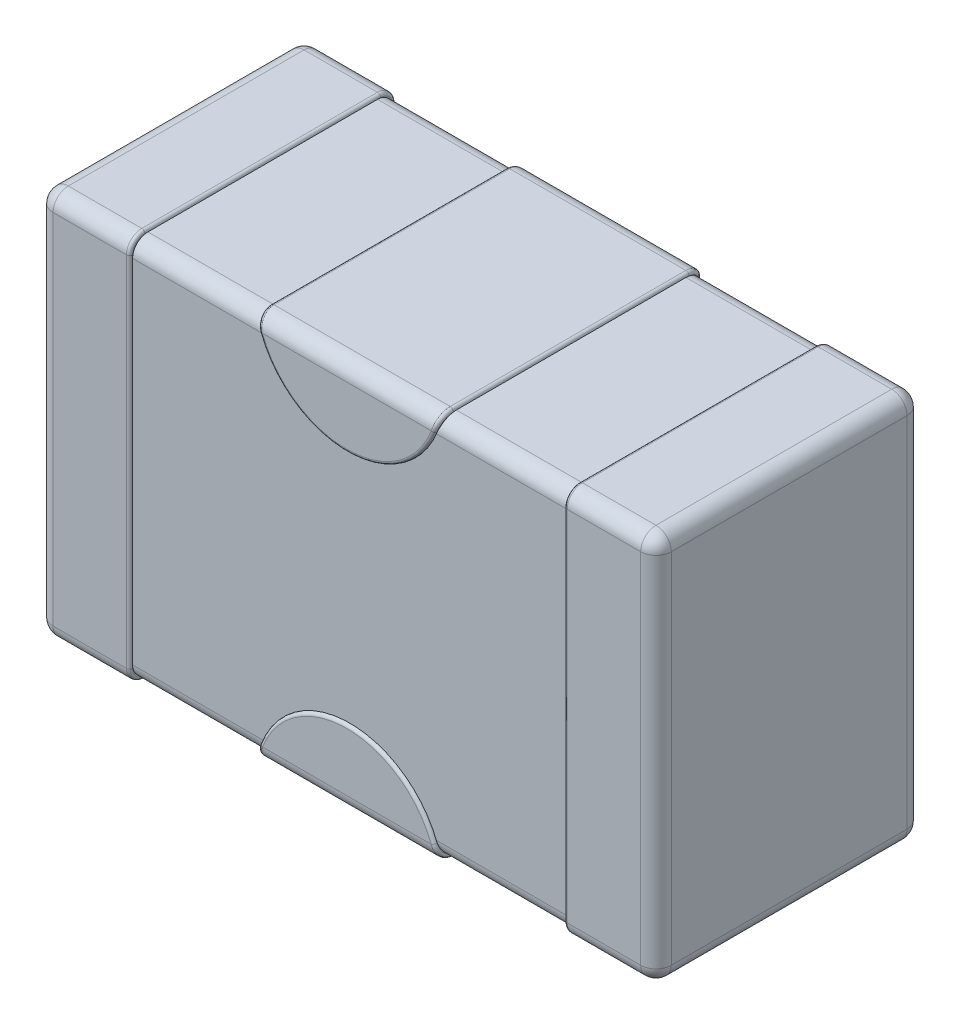
SolidWorks part; units mm, degrees
ref_plane "Front Plane" through (0, 0, 0) normal (0, 0, 1) x (1, 0, 0)
ref_plane "Top Plane" through (0, 0, 0) normal (0, 1, 0) x (1, 0, 0)
ref_plane "Right Plane" through (0, 0, 0) normal (1, 0, 0) x (0, 0, -1)
ref_plane "Плоскость1" through (0, 0, 0.01) normal (0, 0, 1) x (1, 0, 0)
sketch "Sketch1" plane through (0, 0, 0) normal (0, 0, 1) x (1, 0, 0)
  line L1 (-0.005, 0.005) -> (0.005, 0.005)
  line L2 (-0.005, 0.005) -> (-0.005, -0.005)
  line L3 (-0.005, -0.005) -> (0.005, -0.005)
  line L4 (0.005, 0.005) -> (0.005, -0.005)
  line L5 (-0.005, 0.005) -> (0.005, -0.005) construction
  line L6 (-0.005, -0.005) -> (0.005, 0.005) construction
  point P0 (0, 0)
  dimension "D1" = 0.01
sketch "Sketch2" plane through (0, 0, 0.01) normal (0, 0, 1) x (1, 0, 0)
  line L1 (-1, 0.625) -> (1, 0.625)
  line L2 (-1, 0.625) -> (-1, -0.625)
  line L3 (-1, -0.625) -> (1, -0.625)
  line L4 (1, 0.625) -> (1, -0.625)
  line L5 (-1, 0.625) -> (1, -0.625) construction
  line L6 (-1, -0.625) -> (1, 0.625) construction
  point P0 (0, 0)
  dimension "D1" = 1.25
  dimension "D2" = 2
extrude "Boss-Extrude2" add sketch "Sketch2" along normal blind 0.85
sketch "Sketch3" plane through (0, 0, 0) normal (0, 0, 1) x (1, 0, 0)
  line L0 (0, 0) -> (50000, 0) construction
  line L1 (1, 0.625) -> (-1, 0.625) construction
  line L2 (1.01, 0.635) -> (0.71, 0.635)
  line L3 (1.01, 0.635) -> (1.01, -0.635)
  line L4 (1.01, -0.635) -> (0.71, -0.635)
  line L5 (0.71, 0.635) -> (0.71, -0.635)
  line L6 (1, -0.625) -> (1, 0.625) construction
  line L7 (0, 0) -> (0, 50000) construction
  line L8 (-0.71, 0.635) -> (-0.71, -0.635)
  line L9 (-1.01, -0.635) -> (-0.71, -0.635)
  line L10 (-1.01, 0.635) -> (-1.01, -0.635)
  line L11 (-1.01, 0.635) -> (-0.71, 0.635)
  line L12 (-0.3, 0.635) -> (0.3, 0.635)
  line L13 (-0.3, -0.635) -> (0.3, -0.635)
  arc A0 (0.3, 0.635) -> (-0.3, 0.635) centre (0, 0.69) cw
  arc A1 (0.3, -0.635) -> (-0.3, -0.635) centre (0, -0.69) ccw
  point P20 (0, 0.385)
  point P24 (0, -0.385)
  dimension "D1" = 0.01
  dimension "D2" = 0.01
  dimension "D3" = 0.3
  dimension "D4" = 0.25
  dimension "D5" = 0.6
extrude "Boss-Extrude3" add sketch "Sketch3" along normal blind 0.87 separate body
fillet "Fillet1" radius 0.05 4 edges at (1.01, -0.635, 0.435) (1.01, 0.635, 0.435) (1.01, 0, 0) (1.01, 0, 0.87)
fillet "Fillet2" radius 0.05 4 edges at (1, -0.625, 0.435) (1, 0, 0.86) (1, 0.625, 0.435) (1, 0, 0.01)
fillet "Fillet3" radius 0.05 4 edges at (-1.01, 0.635, 0.435) (-1.01, 0, 0.87) (-1.01, -0.635, 0.435) (-1.01, 0, 0)
fillet "Fillet4" radius 0.05 4 edges at (-1, 0.625, 0.435) (-1, 0, 0.86) (-1, -0.625, 0.435) (-1, 0, 0.01)
fillet "Fillet5" radius 0.05 2 edges at (0, 0.635, 0.87) (0, 0.635, 0)
fillet "Fillet7" radius 0.05 2 edges at (0, -0.635, 0) (0, -0.635, 0.87)
fillet "Fillet8" radius 0.05 2 edges at (-0.9954, 0.6204, 0.0146) (-0.835, 0.635, 0)
fillet "Fillet9" radius 0.05 6 edges at (-0.835, 0.635, 0.87) (-0.835, -0.635, 0.87) (-0.835, -0.635, 0) (-0.9954, 0.6204, 0.8554) (-0.9954, -0.6204, 0.8554) (-0.9954, -0.6204, 0.0146)
fillet "Fillet10" radius 0.05 12 edges at (0.9854, 0.6104, 0.0246) (-0.9854, 0.6104, 0.0246) (0, 0.625, 0.01) (0.9854, 0.6104, 0.8454) (-0.9854, 0.6104, 0.8454) (-0.9854, -0.6104, 0.8454) (0.9854, -0.6104, 0.8454) (-0.9854, -0.6104, 0.0246) (0.9854, -0.6104, 0.0246) (0, 0.625, 0.86) (0, -0.625, 0.86) (0, -0.625, 0.01)
fillet "Fillet11" radius 0.05 8 edges at (0.9954, -0.6204, 0.8554) (0.9954, 0.6204, 0.8554) (0.9954, 0.6204, 0.0146) (0.9954, -0.6204, 0.0146) (0.835, -0.635, 0.87) (0.835, 0.635, 0.87) (0.835, 0.635, 0) (0.835, -0.635, 0)
fillet "Fillet12" radius 0.01 8 edges at (0.2961, -0.6169, 0.8585) (0, -0.385, 0.87) (-0.2979, -0.6244, 0.8508) (-0.3, -0.635, 0.435) (-0.2961, -0.6169, 0.0115) (0, -0.385, 0) (0.2979, -0.6244, 0.0192) (0.3, -0.635, 0.435)
fillet "Fillet13" radius 0.01 8 edges at (-0.71, -0.635, 0.435) (-0.71, -0.6204, 0.8554) (-0.71, 0, 0.87) (-0.71, 0.6204, 0.8554) (-0.71, 0.635, 0.435) (-0.71, 0.6204, 0.0146) (-0.71, 0, 0) (-0.71, -0.6204, 0.0146)
fillet "Fillet14" radius 0.01 8 edges at (-0.2979, 0.6244, 0.0192) (-0.3, 0.635, 0.435) (-0.2961, 0.6169, 0.8585) (0, 0.385, 0.87) (0.2979, 0.6244, 0.8508) (0.3, 0.635, 0.435) (0.2961, 0.6169, 0.0115) (0, 0.385, 0)
fillet "Fillet15" radius 0.01 8 edges at (0.71, -0.6204, 0.8554) (0.71, 0, 0.87) (0.71, 0.6204, 0.8554) (0.71, 0.635, 0.435) (0.71, 0.6204, 0.0146) (0.71, 0, 0) (0.71, -0.6204, 0.0146) (0.71, -0.635, 0.435)
